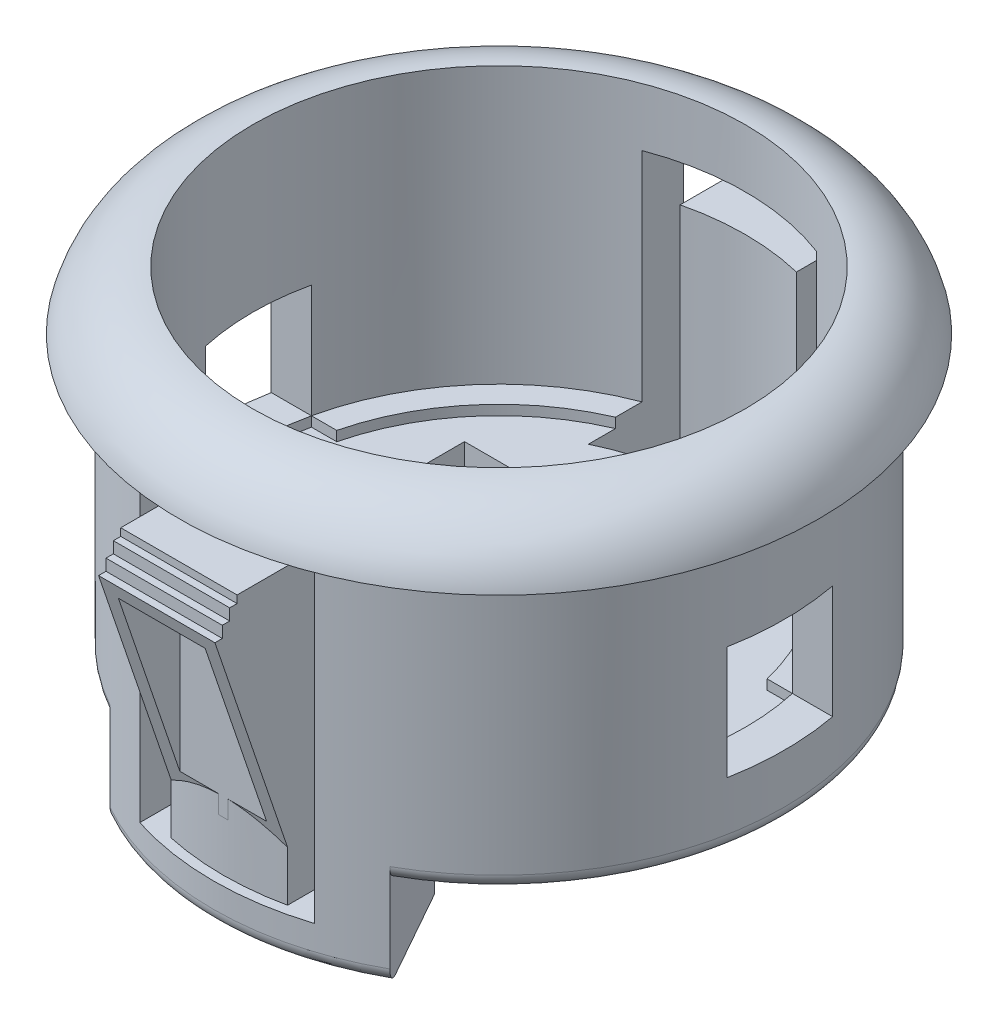
SolidWorks part; units mm, degrees
ref_plane "Front" through (0, 0, 0) normal (0, 0, 1) x (1, 0, 0)
ref_plane "Top" through (0, 0, 0) normal (0, 1, 0) x (1, 0, 0)
ref_plane "Right" through (0, 0, 0) normal (1, 0, 0) x (0, 0, -1)
sketch "Sketch1" plane through (0, 0, 0) normal (0, 0, 1) x (1, 0, 0)
  line L0 (14.732, 0) -> (16.51, 0)
  line L1 (12.7, 3) -> (12.7, -11.224)
  line L2 (12.7, 3) -> (0, 3) construction
  line L3 (14.732, 0) -> (14.732, -19.098)
  line L4 (14.732, -19.098) -> (8.6995, -19.098)
  line L5 (8.6995, -19.098) -> (8.6995, -14.526)
  line L6 (8.6995, -14.526) -> (0, -14.526)
  line L7 (12.7, -11.224) -> (0, -11.224)
  line L8 (0, 3) -> (0, -47.7375) construction
  line L9 (0, -11.224) -> (0, -14.526)
  arc A0 (16.51, 0) -> (12.7, 3) centre (12.7, -0.9194) ccw
  dimension "D1" = 16.51
  dimension "D2" = 3
  dimension "D3" = 17.526
  dimension "D4" = 22.098
  dimension "D5" = 8.6995
  dimension "D6" = 12.7
  dimension "D7" = 14.732
  dimension "D8" = 14.224
  dimension "D9" = 3.81
revolve "Revolve1" add sketch "Sketch1" angle 360 about L8
sketch "Sketch3" plane through (0, -19.098, 0) normal (0, -1, 0) x (1, 0, 0)
  line L0 (-7.2136, -12.8451) -> (7.2136, 12.8451)
  line L1 (-7.2136, 12.8451) -> (7.2136, -12.8451)
  line L2 (0, -14.732) -> (0, 14.732) construction
  line L3 (-7.2136, 12.8451) -> (7.2136, 12.8451) construction
  circle A0 centre (0, 0) radius 14.732 construction
  point P6 (0, 0)
  point P10 (0, 12.8451)
  circle M1 centre (0, 0) radius 14.732
  circle M2 centre (0, 0) radius 8.6995
  dimension "D1" = 14.4272
extrude "feet" cut sketch "Sketch3" against normal up to surface (4.572 mm away) contours L1 L0 M2 M1 | L1 L0 M1 M2 region at (-9.8582, -19.098, 0) region at (9.8582, -19.098, 0) up to face at (-8.6995, -14.526, 0)
sketch "Sketch2" plane through (0, -14.526, 0) normal (0, -1, 0) x (1, 0, 0)
  line L0 (0, 6.0325) -> (0, -6.0325) construction
  line L1 (6.477, 6.0325) -> (-6.477, 6.0325)
  line L2 (6.477, 6.0325) -> (6.477, -6.0325)
  line L3 (6.477, -6.0325) -> (-6.477, -6.0325)
  line L4 (-6.477, 6.0325) -> (-6.477, -6.0325)
  point P6 (0, 0)
  dimension "D1" = 12.065
  dimension "D2" = 12.954
extrude "switch hole" cut sketch "Sketch2" against normal up to next
sketch "Sketch6" plane through (0, 0, 0) normal (1, 0, 0) x (0, 0, -1)
  line L1 (-2.7305, -5.382) -> (2.7305, -5.382)
  line L2 (-2.7305, -5.382) -> (-2.7305, -11.224)
  line L3 (-2.7305, -11.224) -> (2.7305, -11.224)
  line L4 (2.7305, -5.382) -> (2.7305, -11.224)
  line L5 (0, 0) -> (0, -5.382) construction
  line L6 (6.0325, -11.224) -> (-6.0325, -11.224) construction
  dimension "D2" = 5.842
  dimension "D3" = 5.461
extrude "square" cut sketch "Sketch6" against normal through all and the other way through all
sketch "Sketch4" plane through (0, -11.224, 0) normal (0, 1, 0) x (1, 0, 0)
  line L0 (0, 2.7305) -> (12.403, 2.7305)
  line L1 (0, 2.7305) -> (-12.403, 2.7305)
  line L2 (0, -2.7305) -> (12.403, -2.7305)
  line L3 (0, 2.7305) -> (0, -2.7305) construction
  line L4 (0, -2.7305) -> (-12.403, -2.7305)
  line L5 (12.403, -2.7305) -> (14.4767, -2.7305) construction
  circle A0 centre (0, 0) radius 11.43
  circle A2 centre (0, 0) radius 12.7 construction
  circle A3 centre (0, 0) radius 12.7
  point P7 (0, 0)
  dimension "D1" = 1.27
extrude "Extrude3" cut sketch "Sketch4" against normal blind 0.508 contours A0 L2 L0 | A0 L1 L4 | A0 region at (11.9602, -11.224, 0) region at (-11.9602, -11.224, 0)
sketch "Sketch5" plane through (0, -11.732, 0) normal (0, 1, 0) x (1, 0, 0)
  line L0 (6.477, -6.0325) -> (-6.477, -6.0325) construction
  line L1 (7.8105, 6.0325) -> (-7.8105, 6.0325)
  line L2 (7.8105, 6.0325) -> (7.8105, -6.0325)
  line L3 (7.8105, -6.0325) -> (-7.8105, -6.0325)
  line L4 (-7.8105, 6.0325) -> (-7.8105, -6.0325)
  line L5 (-6.477, 6.0325) -> (6.477, 6.0325) construction
  line L6 (0, 6.0325) -> (0, -6.0325) construction
  point P10 (0, 0)
  dimension "D1" = 15.621
extrude "switch hole2" cut sketch "Sketch5" against normal offset from surface (1.524 mm away) 1.27
sketch "Sketch7" plane through (0, 0, 0) normal (0, -1, 0) x (1, 0, 0)
  line L4 (3, 13.904) -> (3, 12.3406)
  line L5 (0, 0) -> (0, 14.732) construction
  line L6 (4.5, 14.0279) -> (4.5, 9.1091)
  line L7 (-4.5, 9.1091) -> (-4.5, 14.0279)
  line L8 (4.5, 9.1091) -> (-4.5, 9.1091) construction
  line L9 (-3, 13.904) -> (-3, 12.3406)
  circle A2 centre (0, 0) radius 14.732 construction
  circle A3 centre (0, 0) radius 10.16
  circle A4 centre (0, 0) radius 14.732
  arc A5 (-3, 13.904) -> (3, 13.904) centre (0, 0) cw
  circle A6 centre (0, 0) radius 12.7 construction
  circle A7 centre (0, 0) radius 12.7
  point P6 (0, 9.1091)
  point P16 (0, 14.224)
  circle M5 centre (0, 0) radius 14.732
  dimension "D2" = 0.508
  dimension "D1" = 20.32
  dimension "D3" = 9
  dimension "D4" = 6
extrude "tab circ cutout" cut sketch "Sketch7" along normal offset from surface (17.066 mm away) 2.032 contours A7 L6 L7 A5 M5 | L6 A7 L7 A3 region at (0, 0, 14.3184) region at (0, 0, 11.1161)
sketch "Sketch9" plane through (3, 0, 0) normal (1, 0, 0) x (0, 0, -1)
  line L1 (-12.3406, 0) -> (-14.8806, 0)
  line L2 (-12.3406, 0) -> (-12.3406, -1.905)
  line L3 (-12.3406, -1.905) -> (-14.8806, -1.905)
  line L4 (-14.8806, 0) -> (-14.8806, -1.905)
  dimension "D1" = 1.905
  dimension "D2" = 2.54
extrude "tab top" cut sketch "Sketch9" against normal up to next
sketch "Sketch10" plane through (0, 0, 0) normal (1, 0, 0) x (0, 0, -1)
  line L0 (-13.904, -14.478) -> (-17.6511, -3.4682)
  line L1 (-13.904, -17.066) -> (-13.904, -14.478) construction
  line L2 (-17.6511, -3.4682) -> (-17.2701, -3.4682)
  line L3 (-17.2701, -3.4682) -> (-17.2701, -2.8794)
  line L4 (-17.2701, -2.8794) -> (-16.8891, -2.8794)
  line L5 (-16.8891, -2.8794) -> (-16.8891, -2.2906)
  line L6 (-16.8891, -2.2906) -> (-16.5081, -2.2906)
  line L7 (-16.5081, -2.2906) -> (-16.5081, -1.905)
  line L8 (-16.5081, -1.905) -> (-13.904, -1.905)
  line L9 (-13.904, -1.905) -> (-13.904, -14.478)
  line L10 (0, 0) -> (0, -28.6281) construction
  line L11 (-13.904, -1.905) -> (-12.3406, -1.905) construction
  line L12 (-12.3406, -1.905) -> (-12.7, -1.905) construction
  line L19 (-13.904, -17.066) -> (-14.224, -17.066) construction
  line L20 (-13.904, -17.066) -> (-14.224, -17.066)
  point P11 (-12.5203, -1.905)
  dimension "D1" = 0.381
  dimension "D2" = 5.1308
  dimension "D3" = 12.573
extrude "tab wedge" add sketch "Sketch10" along normal mid plane 6 contours L9 L8 L7 L6 L5 L4 L3 L2 L0 region at (0, -6.3135, 15.2059)
ref_plane "Plane1" through (0, 0, 17.7781) normal (0, 0, 1) x (1, 0, 0)
sketch "Sketch11" plane through (0, 0, 17.7781) normal (0, 0, 1) x (1, 0, 0)
  line L6 (-2.238, -14.478) -> (2.238, -14.478)
  line L9 (2.238, -4.2302) -> (2.238, -14.478)
  line L10 (-2.238, -4.2302) -> (2.238, -4.2302)
  line L11 (-2.238, -14.478) -> (-2.238, -4.2302)
  line L12 (2.238, -4.2302) -> (2.238, -14.478)
  line L13 (-2.238, -4.2302) -> (2.238, -4.2302)
  line L14 (-2.238, -14.478) -> (-2.238, -4.2302)
  dimension "D1" = 0.762
extrude "cut tab" cut sketch "Sketch11" against normal blind 3.556
mirror "tab mirror" about plane through (0, 0, 0) normal (0, 0, 1) of "cut tab", "tab top", "tab wedge", "tab circ cutout"
fillet "Fillet1" radius 0.762 4 edges at (0, -19.098, -14.732) (0, -19.098, 14.732) (-14.732, -14.526, 0) (14.732, -14.526, 0)
